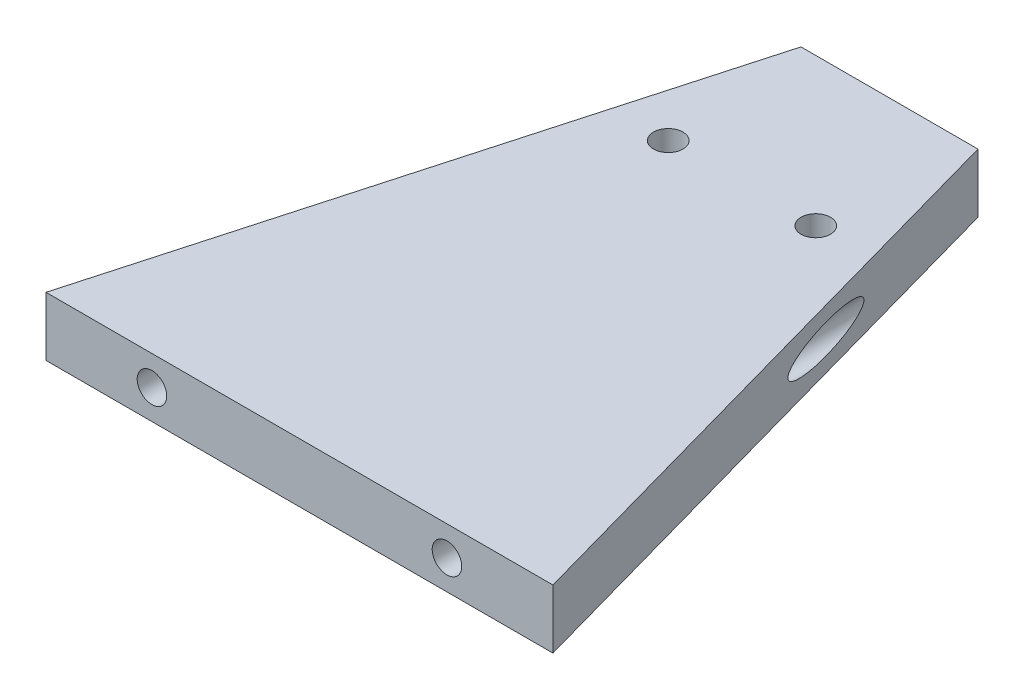
SolidWorks part; units mm, degrees
material "ABS"
ref_plane "Front Plane" through (0, 0, 0) normal (0, 0, 1) x (1, 0, 0)
ref_plane "Top Plane" through (0, 0, 0) normal (0, 1, 0) x (1, 0, 0)
ref_plane "Right Plane" through (0, 0, 0) normal (1, 0, 0) x (0, 0, -1)
sketch "Sketch1" plane through (0, 0, 0) normal (0, 1, 0) x (1, 0, 0)
  line L0 (0, 127) -> (63.5, 127)
  line L1 (63.5, 127) -> (63.5, 0)
  line L2 (63.5, 0) -> (-63.5, 0)
  line L3 (-63.5, 0) -> (-63.5, 127)
  line L4 (-63.5, 127) -> (0, 127)
  line L5 (-63.5, 95.25) -> (-15.875, 95.25) construction
  line L6 (-15.875, 95.25) -> (15.875, 95.25) construction
  line L7 (15.875, 95.25) -> (63.5, 95.25) construction
  circle A0 centre (-15.875, 95.25) radius 3.175
  circle A1 centre (15.875, 95.25) radius 3.175
  dimension "D3" = 6.35
  dimension "D1" = 127
  dimension "D2" = 31.75
  dimension "D4" = 31.75
  dimension "D5" = 127
extrude "Boss-Extrude1" add sketch "Sketch1" along normal blind 12.7
sketch "Sketch3" plane through (0, 0, 0) normal (0, 0, 1) x (1, 0, 0)
  line L0 (-78.7739, 6.35) -> (79.2116, 6.35) construction
  line L1 (-63.5, 12.7) -> (-63.5, 0) construction
  line L2 (63.5, 12.7) -> (63.5, 0) construction
  circle A0 centre (-31.75, 6.35) radius 3.175
  circle A1 centre (31.75, 6.35) radius 3.175
  point P12 (-63.5, 6.35)
  dimension "D1" = 6.35
  dimension "D2" = 31.75
  dimension "D3" = 31.75
extrude "Cut-Extrude1" cut sketch "Sketch3" against normal through all
sketch "Sketch4" plane through (0, 12.7, 0) normal (0, 1, 0) x (1, 0, 0)
  line L0 (-63.5, -32.004) -> (63.5, -32.004) construction
  line L1 (-63.5, 127) -> (-63.5, 0) construction
  line L2 (63.5, 0) -> (63.5, 127) construction
  line L3 (63.5, 127) -> (-63.5, 127) construction
  line L4 (0, 127) -> (19.05, 127) construction
  line L5 (0, 127) -> (-19.05, 127) construction
  line L6 (-63.5, -32.004) -> (-19.05, 127)
  line L7 (19.05, 127) -> (63.5, -32.004)
  line L8 (-63.5, -32.004) -> (-63.5, 127)
  line L9 (-63.5, 127) -> (-19.05, 127)
  line L10 (19.05, 127) -> (63.5, 127)
  line L11 (63.5, 127) -> (63.5, -32.004)
  dimension "D1" = 159.004
  dimension "D2" = 38.1
extrude "Cut-Extrude2" cut sketch "Sketch4" against normal through all
